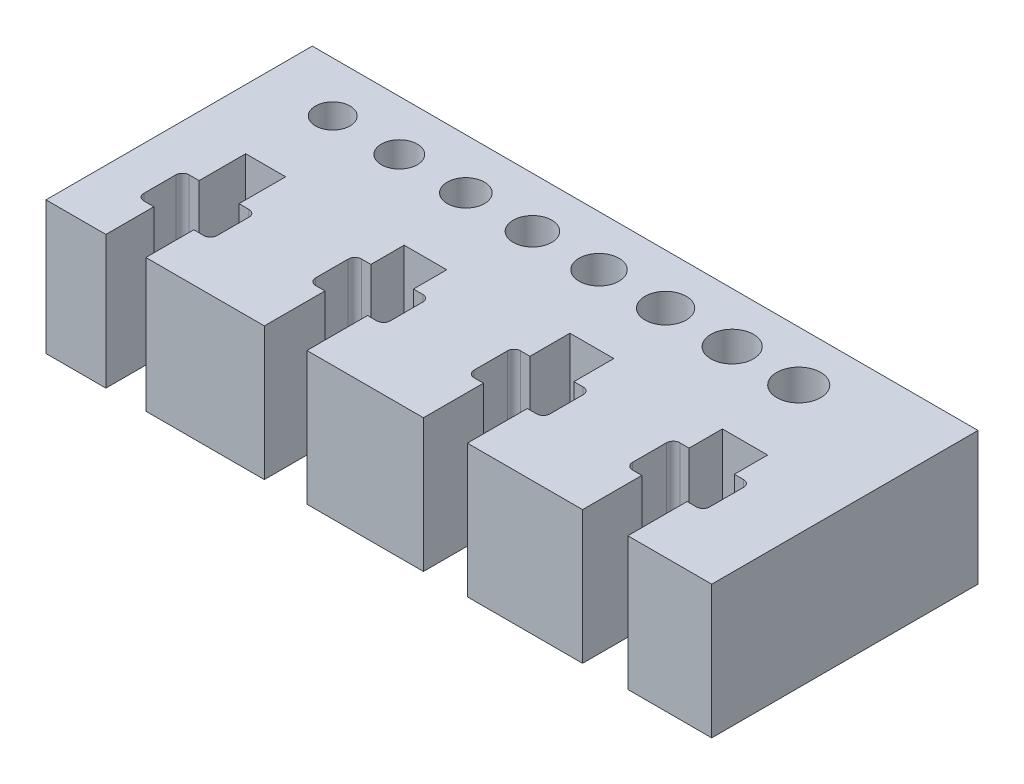
SolidWorks part; units mm, degrees
ref_plane "Front Plane" through (0, 0, 0) normal (0, 0, 1) x (1, 0, 0)
ref_plane "Top Plane" through (0, 0, 0) normal (0, 1, 0) x (1, 0, 0)
ref_plane "Right Plane" through (0, 0, 0) normal (1, 0, 0) x (0, 0, -1)
sketch "Sketch2" plane through (0, 0, 0) normal (0, 1, 0) x (1, 0, 0)
  line L1 (-25, 10) -> (25, 10)
  line L2 (-25, 10) -> (-25, -10)
  line L3 (-25, -10) -> (25, -10)
  line L4 (25, 10) -> (25, -10)
  line L5 (-25, 10) -> (25, -10) construction
  line L6 (-25, -10) -> (25, 10) construction
  point P0 (0, 0)
  dimension "D1" = 50
  dimension "D2" = 20
extrude "Boss-Extrude1" add sketch "Sketch2" along normal blind 10
sketch "Sketch3" plane through (0, 10, 0) normal (0, 1, 0) x (1, 0, 0)
  line L0 (5, -10) -> (5, 1) construction
  line L1 (-25, -10) -> (25, -10) construction
  line L2 (6.65, 1) -> (3.35, 1) construction
  line L3 (3.35, 1) -> (3.35, -10) construction
  line L4 (6.65, -10) -> (3.35, -10)
  line L5 (3.35, -10) -> (3.35, -5.5)
  line L6 (3.35, -5.5) -> (2.65, -5.5)
  line L7 (2.15, -5) -> (2.15, -2.5)
  line L8 (2.65, -2) -> (3.35, -2)
  line L9 (3.35, -2) -> (3.35, 1)
  line L10 (3.35, 1) -> (6.65, 1)
  line L11 (-25, 10) -> (-25, -10) construction
  line L12 (6.65, 1) -> (6.65, -10) construction
  line L13 (6.65, -2) -> (6.65, 1)
  line L14 (7.35, -2) -> (6.65, -2)
  line L15 (7.85, -5) -> (7.85, -2.5)
  line L16 (6.65, -5.5) -> (7.35, -5.5)
  line L17 (6.65, -10) -> (6.65, -5.5)
  line L18 (17, -10) -> (17, 0.5) construction
  line L19 (15.3, 0.5) -> (18.7, 0.5)
  line L20 (15.3, 0.5) -> (15.3, -10) construction
  line L21 (15.3, -10) -> (18.7, -10)
  line L22 (15.3, -10) -> (15.3, -5.55)
  line L23 (15.3, -5.55) -> (14.6, -5.55)
  line L24 (14.1, -5.05) -> (14.1, -2.5)
  line L25 (14.6, -2) -> (15.3, -2)
  line L26 (15.3, -2) -> (15.3, 0.5)
  line L27 (18.7, 0.5) -> (18.7, -10) construction
  line L28 (18.7, -2) -> (18.7, 0.5)
  line L29 (19.4, -2) -> (18.7, -2)
  line L30 (19.9, -5.05) -> (19.9, -2.5)
  line L31 (18.7, -5.55) -> (19.4, -5.55)
  line L32 (18.7, -10) -> (18.7, -5.55)
  line L33 (-7, -10) -> (-7, 0.5) construction
  line L34 (-8.6, 0.5) -> (-5.4, 0.5)
  line L35 (-8.6, 0.5) -> (-8.6, -10) construction
  line L36 (-8.6, -10) -> (-5.4, -10)
  line L37 (-8.6, -10) -> (-8.6, -5.45)
  line L38 (-8.6, -5.45) -> (-9.3, -5.45)
  line L39 (-9.8, -4.95) -> (-9.8, -2.5)
  line L40 (-9.3, -2) -> (-8.6, -2)
  line L41 (-8.6, -2) -> (-8.6, 0.5)
  line L42 (-5.4, 0.5) -> (-5.4, -10) construction
  line L43 (-5.4, -2) -> (-5.4, 0.5)
  line L44 (-4.7, -2) -> (-5.4, -2)
  line L45 (-4.2, -4.95) -> (-4.2, -2.5)
  line L46 (-5.4, -5.45) -> (-4.7, -5.45)
  line L47 (-5.4, -10) -> (-5.4, -5.45)
  line L48 (-19, -10) -> (-19, 0.5) construction
  line L49 (-20.5, 0.5) -> (-17.5, 0.5)
  line L50 (-20.5, 0.5) -> (-20.5, -10) construction
  line L51 (-20.5, -10) -> (-17.5, -10)
  line L52 (-20.5, -10) -> (-20.5, -6.4)
  line L53 (-20.5, -6.4) -> (-21.25, -6.4)
  line L54 (-21.75, -5.9) -> (-21.75, -3.5)
  line L55 (-21.25, -3) -> (-20.5, -3)
  line L56 (-20.5, -3) -> (-20.5, 0.5)
  line L57 (-17.5, 0.5) -> (-17.5, -10) construction
  line L58 (-17.5, -3) -> (-17.5, 0.5)
  line L59 (-16.75, -3) -> (-17.5, -3)
  line L60 (-16.25, -5.9) -> (-16.25, -3.5)
  line L61 (-17.5, -6.4) -> (-16.75, -6.4)
  line L62 (-17.5, -10) -> (-17.5, -6.4)
  line L63 (-25, 6.2223) -> (25, 6.2223) construction
  line L64 (25, -10) -> (25, 10) construction
  arc A0 (2.65, -5.5) -> (2.15, -5) centre (2.65, -5) cw
  arc A1 (2.15, -2.5) -> (2.65, -2) centre (2.65, -2.5) cw
  arc A2 (7.85, -2.5) -> (7.35, -2) centre (7.35, -2.5) ccw
  arc A3 (7.35, -5.5) -> (7.85, -5) centre (7.35, -5) ccw
  arc A4 (14.6, -5.55) -> (14.1, -5.05) centre (14.6, -5.05) cw
  arc A5 (14.1, -2.5) -> (14.6, -2) centre (14.6, -2.5) cw
  arc A6 (19.9, -2.5) -> (19.4, -2) centre (19.4, -2.5) ccw
  arc A7 (19.4, -5.55) -> (19.9, -5.05) centre (19.4, -5.05) ccw
  arc A8 (-9.3, -5.45) -> (-9.8, -4.95) centre (-9.3, -4.95) cw
  arc A9 (-9.8, -2.5) -> (-9.3, -2) centre (-9.3, -2.5) cw
  arc A10 (-4.2, -2.5) -> (-4.7, -2) centre (-4.7, -2.5) ccw
  arc A11 (-4.7, -5.45) -> (-4.2, -4.95) centre (-4.7, -4.95) ccw
  arc A12 (-21.25, -6.4) -> (-21.75, -5.9) centre (-21.25, -5.9) cw
  arc A13 (-21.75, -3.5) -> (-21.25, -3) centre (-21.25, -3.5) cw
  arc A14 (-16.25, -3.5) -> (-16.75, -3) centre (-16.75, -3.5) ccw
  arc A15 (-16.75, -6.4) -> (-16.25, -5.9) centre (-16.75, -5.9) ccw
  circle A16 centre (-19.6857, 6.2223) radius 1.3
  circle A17 centre (-14.6857, 6.2223) radius 1.35
  circle A18 centre (-9.6857, 6.2223) radius 1.4
  circle A19 centre (-4.6857, 6.2223) radius 1.45
  circle A20 centre (0.3143, 6.2223) radius 1.5
  circle A21 centre (5.3143, 6.2223) radius 1.55
  circle A22 centre (10.3143, 6.2223) radius 1.6
  circle A23 centre (15.3143, 6.2223) radius 1.65
  point P14 (2.15, -5.5)
  point P17 (2.15, -2)
  point P28 (7.85, -2)
  point P29 (7.85, -5.5)
  dimension "D7" = 0.5
  dimension "D10" = 0.5
  dimension "D15" = 0.5
  dimension "D22" = 0.5
  dimension "D30" = 2.6
  dimension "D29" = 2.7
  dimension "D31" = 2.8
  dimension "D32" = 2.9
  dimension "D33" = 3
  dimension "D34" = 3.1
  dimension "D35" = 3.2
  dimension "D36" = 3.3
  dimension "D1" = 11
  dimension "D2" = 3.5
  dimension "D3" = 2.85
  dimension "D4" = 1.65
  dimension "D5" = 30
  dimension "D6" = 8
  dimension "D12" = 12
  dimension "D8" = 1.7
  dimension "D9" = 2.9
  dimension "D11" = 3.55
  dimension "D13" = 8
  dimension "D14" = 10.5
  dimension "D16" = 1.6
  dimension "D17" = 3.45
  dimension "D18" = 10.5
  dimension "D19" = 12
  dimension "D20" = 2.8
  dimension "D21" = 8
  dimension "D23" = 3.4
  dimension "D24" = 10.5
  dimension "D25" = 2.75
  dimension "D26" = 7
  dimension "D27" = 1.5
  dimension "D28" = 12
extrude "Cut-Extrude1" cut sketch "Sketch3" against normal through all
equation "\"X-ROD-SPACING\"=45"
equation "\"Y-ROD-SPACING\"=75"
equation "\"Z-ROD-SPACING\"=17.5"
equation "\"Y-BED-OFFSET\"=2"
equation "\"Y-BED-ROD-INSET\"=3.5"
equation "\"Y-BED-SCREW-SPACING\"=209"
equation "\"Y-BED-SCREW-CUTOUT-SLOT-HEIGHT\"=2"
equation "\"T-SLOT-NUT-FILLET-RADIUS\"=0.5"
equation "\"T-SLOT-SCREW-SHAFT-RADIUS\"=1.55"
equation "\"T-SLOT-SCREW-SHAFT-CUTOUT-LENGTH\"=11.0"
equation "\"T-SLOT-NUT-DEPTH\"=3.5"
equation "\"T-SLOT-NUT-WIDTH\"=2.85"
equation "\"T-SLOT-NUT-END-DISTANCE\"=8"
equation "\"ACRYLIC-THICKNESS\"=10"
equation "\"ACRYLIC-THICKNESS2\"=4.5"
equation "\"ACRYLIC-TAB-CUTOUT-SIZE\"=\"ACRYLIC-THICKNESS\"+\"ACRYLIC-TAB-TOLERANCE\"*2"
equation "\"ACRYLIC-TAB-TOLERANCE\"=-.05"
equation "\"ACRYLIC-TAB-WIDTH\"=\"ACRYLIC-THICKNESS\""
equation "\"ACRYLIC-M3-HOLE\"=2.9"
equation "\"SMOOTHROD-CAP-SCREW-DISTANCE\"=20"
equation "\"FRAME-WIDTH-INNER\"=370"
equation "\"NEMA17-HOLE-SPACING\"=31"
equation "\"NEMA17-CENTRAL-CUTOUT\"=22.5"
equation "\"Z-BRACKET-REACH\"=55"
equation "\"Z-ROD-INSET\"=16"
equation "\"TOP-BRACKET-SPACING\"=40"
equation "\"SMOOTHROD-X-LENGTH\"=350"
equation "\"SMOOTHROD-Y-LENGTH\"=350"
equation "\"SMOOTHROD-Z-LENGTH\"=350"
equation "\"SMOOTHROD-TIGHTENING-HEADROOM\"=.25"
equation "\"LEADSCREW-Z-LENGTH\"=300"
equation "\"SCREW-LENGTH-FRAME\"=\"ACRYLIC-THICKNESS\" + 10"
equation "\"SCREW-LENGTH-MOTOR\"=\"ACRYLIC-THICKNESS\" + 5"
equation "\"SCREW-LENGTH-EXTRUDER\"=28"
equation "\"SCREW-HEAD-RADIUS\"=6"
equation "\"PRINTED-M3-HOLE\"=3.5"
equation "\"PRINTED-X-SMOOTHROD-DIAMETER\"=9.4"
equation "\"PRINTED-X-SMOOTHROD-CUTOUT\"=10"
equation "\"PRINTED-X-BASE-HEIGHT\"=10"
equation "\"PRINTED-LM8UU-CUTOUT-SIZE\"=15.5"
equation "\"PRINTED-LM8UU-CUTOUT-LENGTH\"=24.5"
equation "\"PRINTED-X-IDLER-HEIGHT\"=16"
equation "\"PRINTED-M3-NUT-AF\"=6.25"
equation "\"PSU-MOUNTING-WIDTH\"=95"
equation "\"PSU-MOUNTING-HEIGHT\"=177"
equation "\"Y-BELT-TO-ROD-DISTANCE\"=20"
equation "\"SPOOL-HOLDER-ROD-SPACING\"=150"
equation "\"ACRYLIC-X-CARRIAGE-WIDTH\"=55"
equation "\"ACRYLIC-X-CARRIAGE-HEIGHT\"=75"
equation "\"ACRYLIC-X-CARRIAGE-LM8UU-CUTOUT-WIDTH\"=24.25"
equation "\"ACRYLIC-X-CARRIAGE-LM8UU-CUTOUT-HEIGHT\"=11.0"
equation "\"ACRYLIC-X-CARRIAGE-SCREW-SPACING-X\"=15"
equation "\"ACRYLIC-X-CARRIAGE-SCREW-SPACING-Y\"=33"
equation "\"ACRYLIC-X-CARRIAGE-CENTER-TAB-SPACING\"=14"
equation "\"ACRYLIC-X-CARRIAGE-EXTRUDER-OFFSET\"=26"
equation "\"ACRYLIC-X-CARRIAGE-EXTRUDER-ANGLE\"=90"
equation "\"ACRYLIC-X-CARRIAGE-EXTRUDER-SHELF-DEPTH\"=\"ACRYLIC-X-CARRIAGE-EXTRUDER-OFFSET\" + 28"
equation "\"ACRYLIC-X-CARRIAGE-EXTRUDER-BRACE-SPACING\"=23"
equation "\"ACRYLIC-X-CARRIAGE-EXTRUDER-BRACE-TAB-OFFSET\"=20"
equation "\"ACRYLIC-X-CARRIAGE-EXTRUDER-BRACE-HEIGHT\"=35"
equation "\"ACRYLIC-X-CARRIAGE-EXTRUDER-BRACE-SCREW-SPACING\"=22"
equation "\"ACRYLIC-X-CARRIAGE-DUAL-WIDTH-MULTIPLIER\"=1.65"
equation "\"ACRYLIC-X-CARRIAGE-DUAL-HOTEND-SPACING\"=42"
equation "\"ACRYLIC-X-CARRIAGE-DUAL-WIDTH\"=75"
equation "\"ACRYLIC-X-CARRIAGE-DUAL-FAN-OFFSET\"=52"
equation "\"ACRYLIC-X-CARRIAGE-DUAL-FAN-HEIGHT\"=20"
equation "\"ACRYLIC-X-CARRIAGE-DUAL-HOTEND-SEPARATION\"=36"
equation "\"ACRYLIC-X-CARRIAGE-DUAL-MOUNT-PLATE-DEPTH\"=75"
equation "\"ACRYLIC-X-CARRIAGE-DUAL-MOUNT-BRACE-WIDTH\"=33"
equation "\"ACRYLIC-X-CARRIAGE-DUAL-MOUNT-SCREW-WIDTH\"=40"
equation "\"BLOWER-FAN-WIDTH\"=15"
equation "\"D1@Boss-Extrude1\"=\"ACRYLIC-THICKNESS\""
equation "\"D1@Sketch3\"=\"T-SLOT-SCREW-SHAFT-CUTOUT-LENGTH\""
equation "\"D2@Sketch3\"=\"T-SLOT-NUT-DEPTH\""
equation "\"D3@Sketch3\"=\"T-SLOT-NUT-WIDTH\""
equation "\"D6@Sketch3\"=\"T-SLOT-NUT-END-DISTANCE\""
equation "\"D7@Sketch3\"=\"T-SLOT-NUT-FILLET-RADIUS\""
